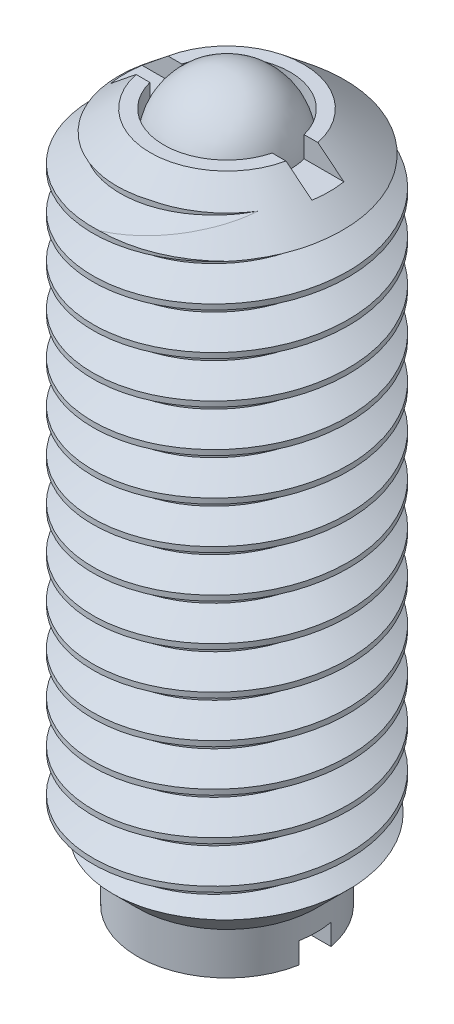
SolidWorks part; units mm, degrees
ref_plane "Front" through (0, 0, 0) normal (0, 0, 1) x (1, 0, 0)
ref_plane "Top" through (0, 0, 0) normal (0, 1, 0) x (1, 0, 0)
ref_plane "Right" through (0, 0, 0) normal (1, 0, 0) x (0, 0, -1)
sketch "Sketch24" plane through (0, 0, 0) normal (1, 0, 0) x (0, 0, -1)
  line L0 (2.413, 6.5151) -> (-2.413, 6.5151) construction
  line L1 (0, 6.5151) -> (2.413, 6.5151)
  line L2 (0, 6.5151) -> (0, -6.5151)
  line L3 (0, -6.5151) -> (2.413, -6.5151)
  line L4 (2.413, 6.5151) -> (2.413, -6.5151)
  point P5 (2.413, 2.9432)
  dimension "Body Length" = 13.0302
  dimension "Screw Dia" = 4.826
  dimension "D1" = 3.5719
revolve "Revolve1" add sketch "Sketch24" angle 360 about L2
sketch "Sketch37" plane through (0, 6.5151, 0) normal (0, 1, 0) x (1, 0, 0)
  circle A1 centre (0, 0) radius 2.413
  circle A2 centre (0, 0) radius 2.413
  dimension "D1" = 0
curve "Helix/Spiral1" pitch 0.7937 height 13.8239 turns 17.416 parameters "pitch"=0.7937
sketch "Sketch38" plane through (0, 0, 0) normal (1, 0, 0) x (0, 0, -1)
  line L0 (-2.413, 7.2096) -> (-2.413, 6.5151)
  line L1 (-2.413, 7.2096) -> (-1.8974, 6.912)
  line L2 (-1.8974, 6.912) -> (-1.8974, 6.8128)
  line L3 (-1.8974, 6.8128) -> (-2.413, 6.5151)
  line L4 (-1.8974, 6.8624) -> (-2.413, 6.8624) construction
  line L5 (-2.1552, 7.0608) -> (-2.1552, 6.6639) construction
  line L6 (2.413, 6.5151) -> (-2.413, 6.5151) construction
  line L7 (0, 0) -> (0, 6.5151) construction
  dimension "D2" = 0.3969
  dimension "D3" = 60
  dimension "D4" = 0.5156
  dimension "D5" = 1.8974
sweep "Cut-Sweep1" cut profiles "Sketch38" path "Helix/Spiral1" align with end faces yes
sketch "Sketch26" plane through (0, 0, 0) normal (1, 0, 0) x (0, 0, -1)
  line L0 (0, -5.2121) -> (0, 6.5151)
  line L1 (0, 6.5151) -> (0, -6.5151) construction
  line L2 (0, 6.5151) -> (1.1938, 6.5151)
  line L3 (1.1938, 6.5151) -> (1.1938, -5.2121)
  line L5 (1.1938, -5.2121) -> (0, -5.2121)
  line L7 (1.1938, 6.5151) -> (-1.1938, 6.5151) construction
  line L8 (2.413, 6.5151) -> (-2.413, 6.5151) construction
  dimension "D1" = 1.303
  dimension "Ball Dia" = 2.3876
revolve "Cut-Revolve10" cut sketch "Sketch26" angle 360 about L0
sketch "Sketch31" plane through (0, 0, 0) normal (1, 0, 0) x (0, 0, -1)
  line L0 (2.413, -6.5151) -> (1.6891, -6.5151)
  line L1 (2.413, 6.5151) -> (2.413, -6.5151) construction
  line L2 (1.6891, -6.5151) -> (1.6891, -5.7213)
  line L3 (0, 0) -> (0, -14.5366) construction
  line L4 (1.6891, -5.7213) -> (2.413, -4.9974)
  line L5 (0, 0) -> (2.413, 0) construction
  line L14 (2.413, 6.5151) -> (1.4478, 6.5151)
  line L15 (0, 6.5151) -> (2.413, 6.5151) construction
  line L16 (1.4478, 6.5151) -> (2.413, 5.7213)
  line L17 (2.413, 5.7213) -> (2.413, 6.5151)
  line L18 (2.413, -4.9974) -> (2.413, -6.5151)
  dimension "D2" = 45
  dimension "D3" = 0.7937
  dimension "D4" = 1.6891
revolve "Cut-Revolve13" cut sketch "Sketch31" angle 360 about L2
sketch "Sketch28" plane through (0, 0, 0) normal (1, 0, 0) x (0, 0, -1)
  line L0 (1.6891, -6.1182) -> (0.3016, -6.1182) construction
  line L1 (-0.3016, -6.5151) -> (0.3016, -6.5151)
  line L2 (-0.3016, -6.5151) -> (-0.3016, -6.1182)
  line L3 (-0.3016, -6.1182) -> (0.3016, -6.1182)
  line L4 (0.3016, -6.5151) -> (0.3016, -6.1182)
  line L5 (2.413, 6.5151) -> (-2.413, 6.5151) construction
  line L6 (-0.3016, 6.5151) -> (0.3016, 6.5151)
  line L7 (-0.3016, 6.5151) -> (-0.3016, 6.1182)
  line L8 (-0.3016, 6.1182) -> (0.3016, 6.1182)
  line L9 (0.3016, 6.5151) -> (0.3016, 6.1182)
  line L10 (1.6891, -6.5151) -> (1.6891, -5.7213) construction
  dimension "D1" = 0.6032
extrude "Cut-Extrude11" cut sketch "Sketch28" against normal through all and the other way through all
sketch "Sketch27" plane through (0, 0, 0) normal (1, 0, 0) x (0, 0, -1)
  line L0 (0, 6.5151) -> (0, -6.5151) construction
  line L1 (1.1938, 6.5151) -> (1.1938, -5.2121) construction
  line L2 (0, -6.5151) -> (0, 4.7625) construction
  line L3 (0, 7.1501) -> (0, 4.7625)
  circle A0 centre (0, 5.9563) radius 1.1938 construction
  arc A1 (0, 7.1501) -> (0, 4.7625) centre (0, 5.9563) cw
  dimension "Ball Projection" = 0.635
revolve "Revolve2" add sketch "Sketch27" angle 360 about L3
ref_plane "Plane1" [suppressed] through (-1.4224, 0, 0) normal (1, 0, 0) x (0, 0, -1)
sketch "Sketch21" [suppressed] plane through (-1.4224, 0, 0) normal (1, 0, 0) x (0, 0, -1)
  line L0 (0, -1.7183) -> (0, -3.2804) construction
  line L2 (1.4224, 2.3749) -> (-1.4224, 2.3749) construction
  line L3 (0, 2.3749) -> (0, -2.3749) construction
  ellipse E0 centre (0, -0.4661) end of major axis (0, 0.4585) minor radius 0.7112
  dimension "D5" = 2.413
  dimension "D6" = 3.1369
  dimension "D7" = 2.8746
sketch "Sketch41" [suppressed] plane through (-1.4224, 0, 0) normal (1, 0, 0) x (0, 0, -1)
  ellipse E1 centre (0, -0.4661) end of major axis (0, 0.4585) minor radius 0.7112
  ellipse E2 centre (0, -0.4661) end of major axis (0, 0.4585) minor radius 0.7112
  dimension "D1" = 0
sketch "Sketch43" [suppressed] plane through (0, 0, 0) normal (1, 0, 0) x (0, 0, -1)
  ellipse E1 centre (0, -0.4661) end of major axis (0, 0.4585) minor radius 0.7112
  ellipse E2 centre (0, -0.4661) end of major axis (0, 0.4585) minor radius 0.7112
  dimension "D1" = 0
extrude "Extrude9" [suppressed] cut sketch "Sketch43" against normal through all
sketch "Sketch44" [suppressed] plane through (0, 0, 0) normal (1, 0, 0) x (0, 0, -1)
  ellipse E1 centre (0, -0.4661) end of major axis (0, 0.4585) minor radius 0.7112
  ellipse E2 centre (0, -0.4661) end of major axis (0, 0.4585) minor radius 0.7112
  dimension "D1" = 0
extrude "Extrude10" [suppressed] add sketch "Sketch44" against normal blind 1.8974 separate body
dome "Dome1" [suppressed] faces to dome 1 distance 0.2578 parameters "D1"=0.2578
sketch "Sketch45" plane through (0, 0, 0) normal (0, 1, 0) x (1, 0, 0)
  circle A0 centre (0, 0) radius 1.1938
  arc A1 (-1.1551, -0.3016) -> (1.1551, -0.3016) centre (0, 0) ccw construction
extrude "Extrude11" [suppressed] cut sketch "Sketch45" against normal through all and the other way through all
equation "\"D1@Sketch26\" = \"Body Length@Sketch24\"*.1"
equation "\"D1@Sketch28\" = \"Screw Dia@Sketch24\"/8"
equation "\"D1@Sketch38\" = \"pitch@Helix/Spiral1\"*.125"
equation "\"D2@Sketch38\" = \"pitch@Helix/Spiral1\"*.50"
equation "\"D3@Helix/Spiral1\" = \"Body Length@Sketch24\"+\"pitch@Helix/Spiral1\""
equation "\"D3@Sketch31\" = \"pitch@Helix/Spiral1\""
equation "\"D4@Sketch31\" = (\"Screw Dia@Sketch24\"/2)*.7"
equation "\"D5@Sketch21\" = \"Screw Dia@Sketch24\"*.50"
equation "\"D6@Sketch21\" = \"D5@Sketch21\"*1.3"
equation "\"D7@Sketch21\" = \"pitch@Helix/Spiral1\"*3.62154"
equation "\"D1@Sketch24\" = \"pitch@Helix/Spiral1\"*4.50"
equation "\"D1@Plane1\" = \"Screw Dia@Sketch24\"/2"
equation "\"D1@Extrude10\" = \"D5@Sketch38\""
equation "\"D1@Dome1\" = \"D6@Sketch38\""
